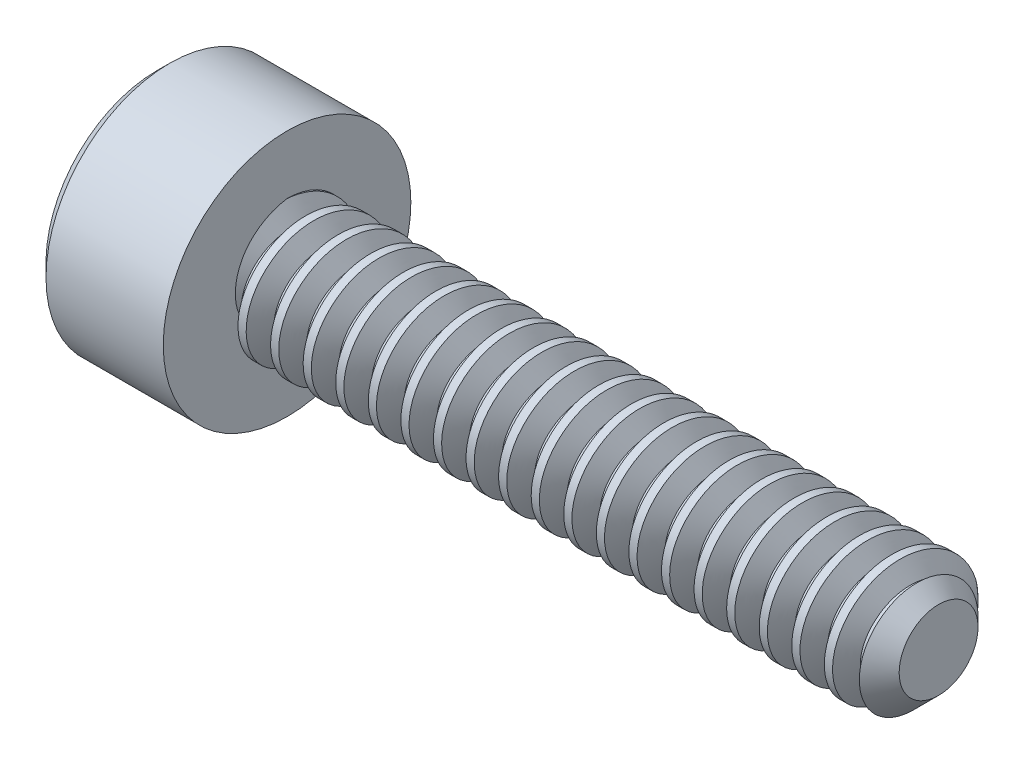
SolidWorks part; units mm, degrees
material "AISI 304"
ref_plane "Front Plane" through (0, 0, 0) normal (0, 0, 1) x (1, 0, 0)
ref_plane "Top Plane" through (0, 0, 0) normal (0, 1, 0) x (1, 0, 0)
ref_plane "Right Plane" through (0, 0, 0) normal (1, 0, 0) x (0, 0, -1)
sketch "Sketch1" plane through (0, 0, 0) normal (0, 0, 1) x (1, 0, 0)
  line L0 (0, 0) -> (0, 1.9)
  line L2 (2, 1) -> (12, 1)
  line L3 (12, 1) -> (12, 0)
  line L4 (12, 0) -> (0, 0)
  line L5 (0, 0) -> (-45.4653, 0) construction
  line L6 (0, 1.9) -> (2, 1.9)
  line L7 (2, 1.9) -> (2, 1)
  dimension "D1" = 3.8
  dimension "D2" = 2
  dimension "D4" = 2
  dimension "D3" = 10
revolve "Revolve1" add sketch "Sketch1" angle 360 about L5
chamfer "Chamfer1" distance 0.395 angle 45 1 edges at (12, 1, 0)
sketch "Sketch2" plane through (12, 0, 0) normal (1, 0, 0) x (0, 0, -1)
  circle A1 centre (0, 0) radius 1
  circle A2 centre (0, 0) radius 1 construction
curve "Helix/Spiral1" pitch 0.5 height 11 turns 22
sketch "Sketch3" plane through (0, 0, 0) normal (0, 0, 1) x (1, 0, 0)
  line L4 (11.9375, 1.1083) -> (12.4375, 1.1083) construction
  line L5 (12.4375, 1.1083) -> (12.1875, 0.6752) construction
  line L6 (12.1875, 0.6752) -> (11.9375, 1.1083) construction
  line L7 (12, 1) -> (12.375, 1) construction
  line L8 (11.605, 1) -> (2, 1) construction
  line L9 (11.9688, 1.0541) -> (12.4063, 1.0541)
  line L10 (12.4063, 1.0541) -> (12.2188, 0.7294)
  line L11 (12.2188, 0.7294) -> (12.1563, 0.7294)
  line L12 (12.1563, 0.7294) -> (11.9688, 1.0541)
  line L13 (12, 1) -> (11.9375, 1.1083) construction
  line L14 (12.1875, 1.0541) -> (12.1875, 1.1083) construction
  line L15 (12.1875, 0.7294) -> (12.1875, 0.6752) construction
  dimension "D1" = 0.5
  dimension "D2" = 0.0625
sweep "Cut-Sweep1" cut profiles "Sketch3" path "Helix/Spiral1"
sketch "Sketch6" plane through (0, 0, 0) normal (-1, 0, 0) x (0, 0, 1)
  circle A1 centre (0, 0) radius 1.9
  circle A2 centre (0, 0) radius 1.9
  dimension "D1" = 0
extrude "Boss-Extrude1" add sketch "Sketch6" against normal up to surface (2 mm away) up to face at (2, 0.3528, -0.2735)
sketch "Sketch4" plane through (0, 0, 0) normal (-1, 0, 0) x (0, 0, 1)
  line L0 (-1.1547, 0) -> (-0.5774, 1)
  line L1 (-0.5774, 1) -> (0.5774, 1)
  line L2 (0.5774, 1) -> (1.1547, 0)
  line L3 (1.1547, 0) -> (0.5774, -1)
  line L4 (0.5774, -1) -> (-0.5774, -1)
  line L5 (-0.5774, -1) -> (-1.1547, 0)
  circle A0 centre (0, 0) radius 1 construction
  dimension "D1" = 2
extrude "Cut-Extrude1" cut sketch "Sketch4" against normal blind 1.6
sketch "Sketch5" plane through (0, 0, 0) normal (-1, 0, 0) x (0, 0, 1)
  circle A0 centre (0, 0) radius 1.1547
extrude "Cut-Extrude2" cut sketch "Sketch5" against normal through all draft 45
chamfer "Chamfer2" distance 0.2 angle 45 1 edges at (0, 1.9, 0)
equation "\"diam_head\"=0.003800"
equation "\"L_head\"=0.002000"
equation "\"L\"=0.010000"
equation "\"diam_thread\"=0.002000"
equation "\"pitch\"=0.000500"
equation "\"D1@Sketch1\"=\"diam_head\"*1000"
equation "\"D2@Sketch1\"=\"diam_thread\"*1000"
equation "\"D4@Sketch1\"=\"L_head\"*1000"
equation "\"D1@Chamfer1\"=\"pitch\"*1000*0.79"
equation "\"D1@Sketch3\"=\"pitch\"*1000"
equation "\"D3@Helix/Spiral1\"=(\"L\"+0.5*\"L_head\")*1000"
equation "\"D4@Helix/Spiral1\"=\"pitch\"*1000"
equation "\"L_thread\"=0.012000"
equation "\"D1@Cut-Extrude1\"=\"L_head\"*1000*0.8"
equation "\"D1\"=  ( \"L\" - \"L_thread\" )  * 1000"
equation "\"D3@Sketch1\"=\"L\"*1000"
equation "\"D2@Sketch3\"=\"pitch\"*1000/8"
